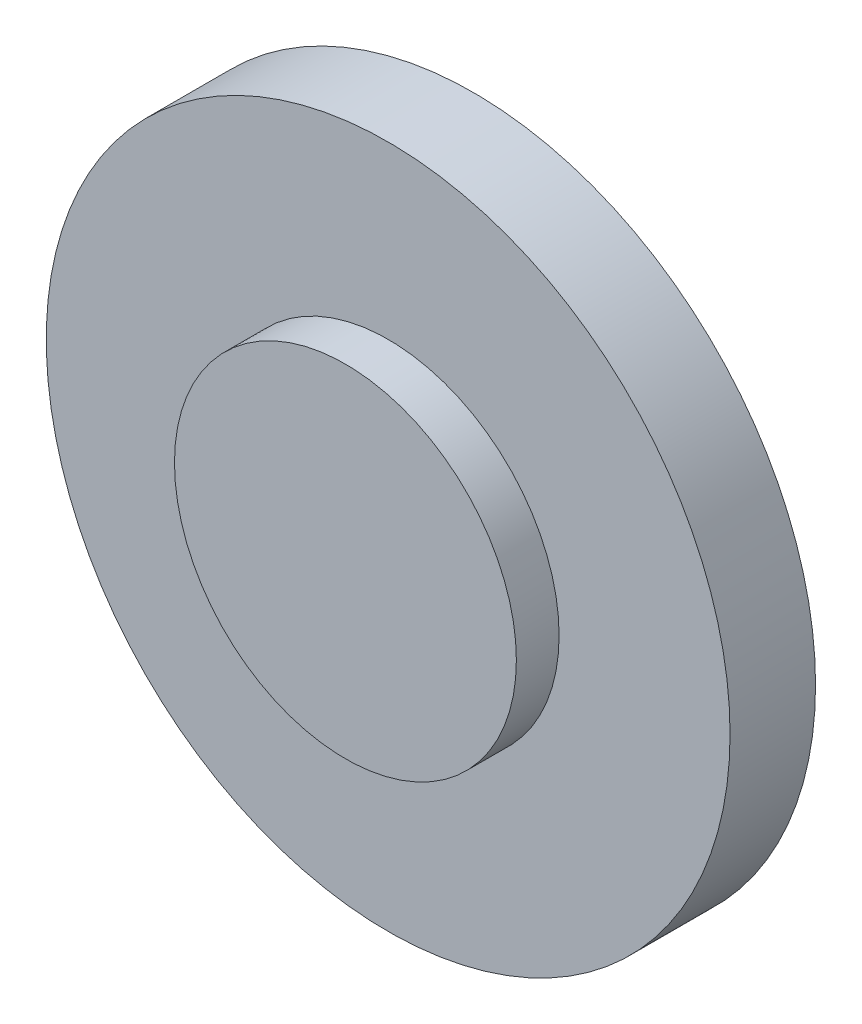
SolidWorks part; units mm, degrees
ref_plane "Plano frontal" through (0, 0, 0) normal (0, 0, 1) x (1, 0, 0)
ref_plane "Plano superior" through (0, 0, 0) normal (0, 1, 0) x (1, 0, 0)
ref_plane "Plano direito" through (0, 0, 0) normal (1, 0, 0) x (0, 0, -1)
sketch "Esboço1" plane through (0, 0, 0) normal (0, 0, 1) x (1, 0, 0)
  circle A0 centre (0, 0) radius 4
  dimension "D1" = 8
extrude "Ressalto-extrusão1" add sketch "Esboço1" along normal blind 1
sketch "Esboço2" plane through (0, 0, 1) normal (0, 0, 1) x (1, 0, 0)
  circle A0 centre (0, 0) radius 2
  dimension "D1" = 4
extrude "Ressalto-extrusão2" add sketch "Esboço2" along normal blind 0.5
